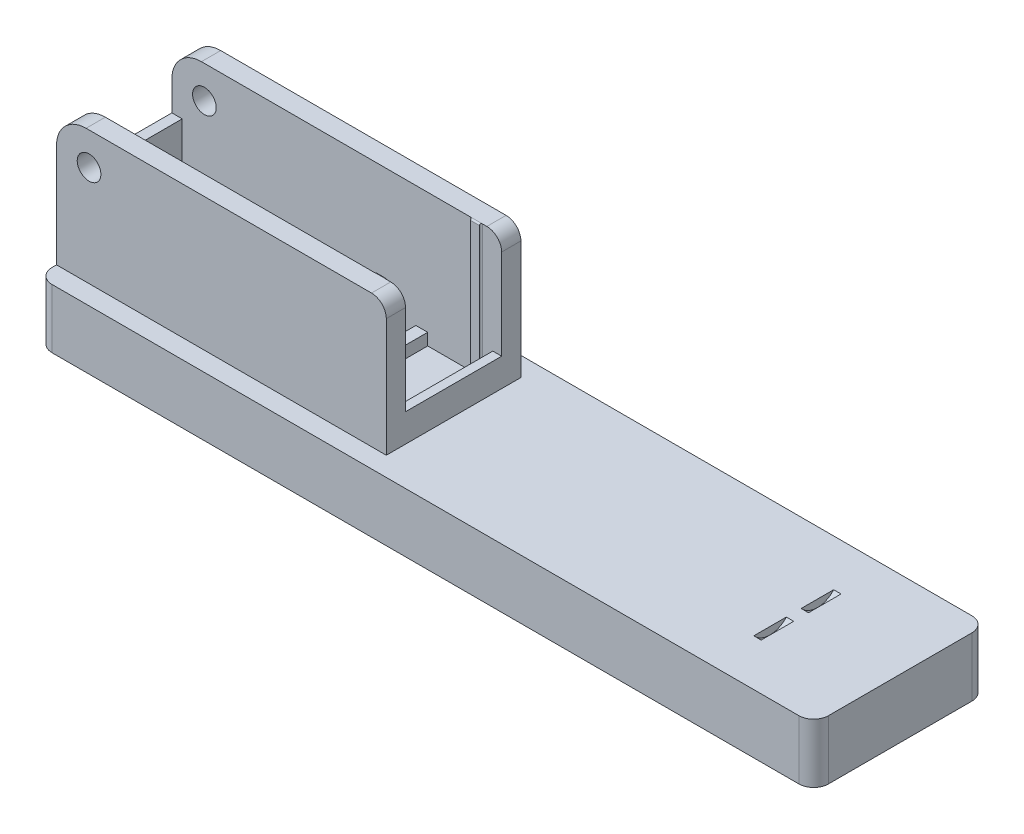
SolidWorks part; units mm, degrees
material "Polyethylene Cross-Linked"
ref_plane "Front Plane" through (0, 0, 0) normal (0, 0, 1) x (1, 0, 0)
ref_plane "Top Plane" through (0, 0, 0) normal (0, 1, 0) x (1, 0, 0)
ref_plane "Right Plane" through (0, 0, 0) normal (1, 0, 0) x (0, 0, -1)
sketch "Sketch1" plane through (0, 0, 0) normal (0, 1, 0) x (1, 0, 0)
  line L1 (-64.135, 14.859) -> (64.135, 14.859)
  line L2 (-66.675, 12.319) -> (-66.675, -12.319)
  line L3 (-64.135, -14.859) -> (64.135, -14.859)
  line L4 (66.675, 12.319) -> (66.675, -12.319)
  line L5 (-66.675, 14.859) -> (66.675, -14.859) construction
  line L6 (-66.675, -14.859) -> (66.675, 14.859) construction
  arc A0 (-66.675, -12.319) -> (-64.135, -14.859) centre (-64.135, -12.319) ccw
  arc A1 (64.135, -14.859) -> (66.675, -12.319) centre (64.135, -12.319) ccw
  arc A2 (64.135, 14.859) -> (66.675, 12.319) centre (64.135, 12.319) cw
  arc A3 (-64.135, 14.859) -> (-66.675, 12.319) centre (-64.135, 12.319) ccw
  point P0 (0, 0)
  dimension "D3" = 2.54
  dimension "D1" = 133.35
  dimension "D2" = 29.718
extrude "Boss-Extrude1" add sketch "Sketch1" along normal blind 10.16
ref_plane "Plane1" through (0, 0, 11.557) normal (0, 0, 1) x (1, 0, 0)
sketch "Sketch2" plane through (0, 0, 11.557) normal (0, 0, 1) x (1, 0, 0)
  line L0 (-10.033, 10.16) -> (-10.033, 30.48)
  line L1 (-64.135, 10.16) -> (64.135, 10.16) construction
  line L2 (-12.573, 33.02) -> (-61.595, 33.02)
  line L3 (-66.675, 27.94) -> (-66.675, 10.16)
  line L4 (-66.675, 10.16) -> (-10.033, 10.16)
  arc A0 (-61.595, 33.02) -> (-66.675, 27.94) centre (-61.595, 27.94) ccw
  circle A1 centre (-61.087, 27.432) radius 2.032
  arc A2 (-10.033, 30.48) -> (-12.573, 33.02) centre (-12.573, 30.48) ccw
  point P9 (-66.675, 33.02)
  point P15 (-10.033, 33.02)
  dimension "D3" = 5.08
  dimension "D4" = 4.064
  dimension "D7" = 2.54
  dimension "D1" = 56.642
  dimension "D2" = 22.86
  dimension "D5" = 5.588
  dimension "D6" = 5.588
extrude "Boss-Extrude2" add sketch "Sketch2" against normal blind 3.302
sketch "Sketch3" plane through (0, 10.16, 0) normal (0, 1, 0) x (1, 0, 0)
  line L0 (-18.161, 0) -> (18.161, 0) construction
  line L1 (-66.675, -8.255) -> (-64.897, -8.255)
  line L2 (-66.675, -8.255) -> (-66.675, 0)
  line L3 (-66.675, 0) -> (-64.897, 0)
  line L4 (-64.897, -8.255) -> (-64.897, 0)
  dimension "D1" = 1.778
extrude "Boss-Extrude3" add sketch "Sketch3" along normal blind 12.7
sketch "Sketch4" plane through (0, 10.16, 0) normal (0, 1, 0) x (1, 0, 0)
  line L0 (-18.161, 0) -> (18.161, 0) construction
  line L1 (-54.737, 0) -> (-53.213, 0)
  line L2 (-54.737, 0) -> (-54.737, -8.255)
  line L3 (-54.737, -8.255) -> (-53.213, -8.255)
  line L4 (-53.213, 0) -> (-53.213, -8.255)
  line L5 (-12.573, -8.255) -> (-61.595, -8.255) construction
  line L6 (-64.897, -8.255) -> (-64.897, 0) construction
  dimension "D1" = 1.524
  dimension "D2" = 10.16
extrude "Boss-Extrude4" add sketch "Sketch4" along normal blind 2.286
sketch "Sketch5" plane through (0, 10.16, 0) normal (0, 1, 0) x (1, 0, 0)
  line L0 (-18.161, 0) -> (18.161, 0) construction
  line L1 (-48.133, 0) -> (-49.911, 0)
  line L2 (-41.275, 0) -> (-43.053, 0)
  line L3 (-54.737, 0) -> (-54.737, -8.255) construction
  arc A0 (-41.275, 0) -> (-49.911, 0) centre (-45.593, 0) cw
  arc A1 (-43.053, 0) -> (-48.133, 0) centre (-45.593, 0) cw
  dimension "D1" = 4.318
  dimension "D2" = 2.54
  dimension "D3" = 6.604
extrude "Boss-Extrude5" add sketch "Sketch5" along normal blind 2.54
sketch "Sketch6" plane through (0, 10.16, 0) normal (0, 1, 0) x (1, 0, 0)
  line L0 (-18.161, 0) -> (18.161, 0) construction
  line L1 (-33.909, -1.8139) -> (-33.909, -3.6544)
  line L6 (-30.353, -1.8139) -> (-30.353, -3.6544)
  line L7 (-36.195, 0) -> (-34.671, 0)
  line L8 (-29.591, 0) -> (-28.067, 0)
  arc A0 (-30.353, -1.8139) -> (-29.591, 0) centre (-32.131, 0) ccw
  arc A1 (-30.353, -3.6544) -> (-28.067, 0) centre (-32.131, 0) ccw
  arc A2 (-34.671, 0) -> (-33.909, -1.8139) centre (-32.131, 0) ccw
  arc A3 (-36.195, 0) -> (-33.909, -3.6544) centre (-32.131, 0) ccw
  arc A4 (-48.133, 0) -> (-43.053, 0) centre (-45.593, 0) ccw construction
  dimension "D1" = 5.08
  dimension "D2" = 8.128
  dimension "D3" = 10.922
  dimension "D4" = 3.556
extrude "Boss-Extrude6" add sketch "Sketch6" along normal blind 3.556
sketch "Sketch7" plane through (0, 10.16, 0) normal (0, 1, 0) x (1, 0, 0)
  line L0 (-18.161, 0) -> (18.161, 0) construction
  line L1 (-24.765, 0) -> (-22.733, 0)
  line L2 (-24.765, 0) -> (-24.765, -8.255)
  line L3 (-24.765, -8.255) -> (-22.733, -8.255)
  line L4 (-22.733, 0) -> (-22.733, -8.255)
  line L5 (-12.573, -8.255) -> (-61.595, -8.255) construction
  line L6 (-10.033, -8.255) -> (-10.033, -11.557) construction
  dimension "D1" = 2.032
  dimension "D2" = 12.7
extrude "Boss-Extrude7" add sketch "Sketch7" along normal blind 2.032 contours L2 L3 L4 L1
sketch "Sketch8" plane through (0, 10.16, 0) normal (0, 1, 0) x (1, 0, 0)
  line L0 (-18.161, 0) -> (18.161, 0) construction
  line L1 (-10.033, -8.255) -> (-11.557, -8.255)
  line L2 (-10.033, -8.255) -> (-10.033, 0)
  line L3 (-10.033, 0) -> (-11.557, 0)
  line L4 (-11.557, -8.255) -> (-11.557, 0)
  dimension "D1" = 1.524
extrude "Boss-Extrude8" add sketch "Sketch8" along normal blind 4.826
sketch "Sketch9" plane through (0, 0, 8.255) normal (0, 0, -1) x (-1, 0, 0)
  line L0 (12.573, 33.02) -> (61.595, 33.02) construction
  line L1 (13.589, 33.02) -> (15.113, 33.02)
  line L2 (13.589, 33.02) -> (13.589, 10.16)
  line L3 (13.589, 10.16) -> (15.113, 10.16)
  line L4 (15.113, 33.02) -> (15.113, 10.16)
  line L5 (22.733, 10.16) -> (11.557, 10.16) construction
  line L6 (10.033, 14.986) -> (10.033, 30.48) construction
  dimension "D1" = 1.524
  dimension "D2" = 3.556
extrude "Boss-Extrude9" add sketch "Sketch9" along normal blind 0.254
fillet "Fillet2" radius 0.254 2 edges at (-13.589, 21.59, 8.255) (-15.113, 21.59, 8.255)
fillet "Fillet4" radius 0.254 1 edges at (-14.351, 33.02, 8.001)
mirror "Mirror1" about plane through (0, 0, 0) normal (0, 0, 1) of "Fillet4", "Fillet2", "Boss-Extrude9", "Boss-Extrude8", "Boss-Extrude7", "Boss-Extrude6", "Boss-Extrude5", "Boss-Extrude3", "Boss-Extrude4", "Boss-Extrude2"
ref_plane "Plane2" through (49.657, 0, 0) normal (1, 0, 0) x (0, 0, -1)
sketch "Sketch10" plane through (49.657, 0, 0) normal (1, 0, 0) x (0, 0, -1)
  line L6 (0, 18.161) -> (0, -18.161) construction
  line L8 (-4.064, 8.89) -> (-6.604, 8.89) construction
  line L9 (11.557, 10.16) -> (-11.557, 10.16) construction
  line L10 (-6.858, 10.16) -> (-1.27, 10.16) construction
  line L11 (-12.319, 10.16) -> (12.319, 10.16) construction
  circle A0 centre (-4.064, 12.5984) radius 3.7084
  dimension "D1" = 1.27
  dimension "D2" = 4.064
  dimension "D3" = 5.588
  dimension "D4" = 2.54
extrude "Cut-Extrude1" cut sketch "Sketch10" against normal blind 1.27
mirror "Mirror2" about plane through (0, 0, 0) normal (0, 0, 1) of "Cut-Extrude1"
